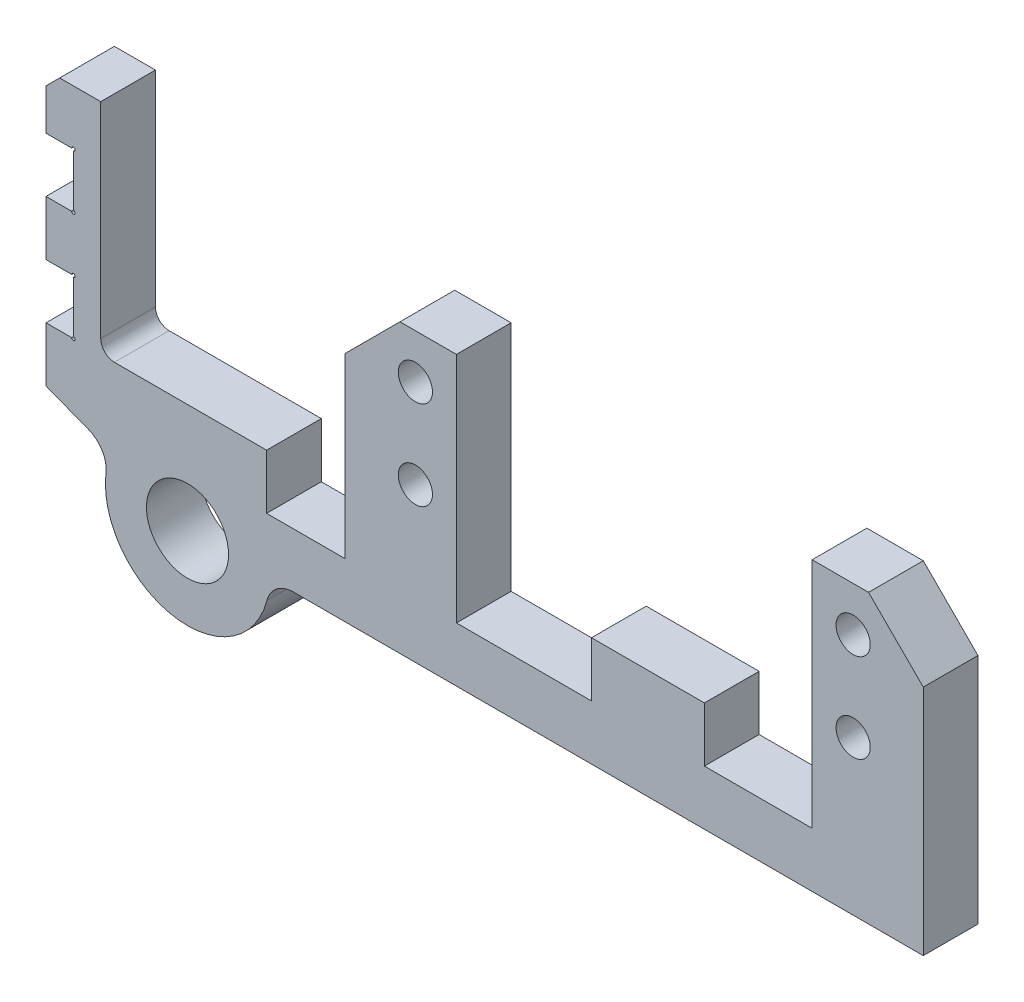
SolidWorks part; units mm, degrees
ref_plane "Front Plane" through (0, 0, 0) normal (0, 0, 1) x (1, 0, 0)
ref_plane "Top Plane" through (0, 0, 0) normal (0, 1, 0) x (1, 0, 0)
ref_plane "Right Plane" through (0, 0, 0) normal (1, 0, 0) x (0, 0, -1)
sketch "Sketch1" plane through (0, 136.6763, 0) normal (0, 1, 0) x (1, 0, 0)
  line L0 (-27.651, -32.4827) -> (-27.651, -60.4545) construction
  line L1 (-103.851, -54.1033) -> (-90.951, -54.1033)
  line L2 (-103.851, -54.1033) -> (-103.851, -60.4533)
  line L3 (-103.851, -60.4533) -> (-90.951, -60.4533)
  line L4 (-90.951, -54.1033) -> (-90.951, -60.4533)
  line L5 (-68.926, -54.1033) -> (-81.826, -54.1033)
  line L6 (-68.926, -54.1033) -> (-68.926, -60.4533)
  line L7 (-68.926, -60.4533) -> (-81.826, -60.4533)
  line L8 (-81.826, -54.1033) -> (-81.826, -60.4533)
  line L9 (-53.251, -54.1033) -> (-40.151, -54.1033)
  line L10 (-53.251, -54.1033) -> (-53.251, -60.4533)
  line L11 (-53.251, -60.4533) -> (-40.151, -60.4533)
  line L12 (-40.151, -54.1033) -> (-40.151, -60.4533)
  line L13 (-27.651, -54.1033) -> (-14.751, -54.1033)
  line L14 (-27.651, -54.1033) -> (-27.651, -60.4533)
  line L15 (-27.651, -60.4533) -> (-14.751, -60.4533)
  line L16 (-14.751, -54.1033) -> (-14.751, -60.4533)
  dimension "D1" = 12.9
  dimension "D2" = 13.1
  dimension "D3" = 12.9
  dimension "D4" = 12.9
  dimension "D5" = 50.6
extrude "Boss-Extrude1" add sketch "Sketch1" against normal blind 6.35
sketch "Sketch2" plane through (0, 130.3263, 0) normal (0, -1, 0) x (-1, 0, 0)
  line L1 (103.851, -60.4533) -> (14.951, -60.4533)
  line L2 (103.851, -60.4533) -> (103.851, -54.1033)
  line L3 (103.851, -54.1033) -> (14.951, -54.1033)
  line L4 (14.951, -60.4533) -> (14.951, -54.1033)
  dimension "D1" = 6.35
  dimension "D2" = 88.9
extrude "Boss-Extrude2" add sketch "Sketch2" along normal blind 12.7
sketch "Sketch3" plane through (0, 136.6763, 0) normal (0, 1, 0) x (1, 0, 0)
  line L1 (-68.926, -54.1033) -> (-81.826, -54.1033)
  line L2 (-68.926, -54.1033) -> (-68.926, -60.4533)
  line L3 (-68.926, -60.4533) -> (-81.826, -60.4533)
  line L4 (-81.826, -54.1033) -> (-81.826, -60.4533)
  line L5 (-14.751, -54.1033) -> (-27.651, -54.1033)
  line L6 (-14.751, -54.1033) -> (-14.751, -60.4533)
  line L7 (-14.751, -60.4533) -> (-27.651, -60.4533)
  line L8 (-27.651, -54.1033) -> (-27.651, -60.4533)
extrude "Boss-Extrude3" add sketch "Sketch3" along normal up to surface (20.6375 mm away)
chamfer "Chamfer1" distance 6.35 angle 45 2 edges at (-14.751, 157.3138, 57.2783) (-81.826, 157.3138, 57.2783)
sketch "Sketch4" plane through (0, 0, 60.4533) normal (0, 0, 1) x (1, 0, 0)
  circle A0 centre (-73.6885, 152.1544) radius 1.9844
  circle A1 centre (-73.6885, 141.8357) radius 1.9844
  circle A2 centre (-22.8885, 141.8357) radius 1.9844
  circle A3 centre (-22.8885, 152.1544) radius 1.9844
extrude "Cut-Extrude1" cut sketch "Sketch4" against normal through all
sketch "Sketch12" plane through (-14.951, 0, 0) normal (1, 0, 0) x (0, 0, -1)
  line L1 (-60.4533, 117.6263) -> (-54.1033, 117.6263)
  line L2 (-60.4533, 117.6263) -> (-60.4533, 130.3263)
  line L3 (-60.4533, 130.3263) -> (-54.1033, 130.3263)
  line L4 (-54.1033, 117.6263) -> (-54.1033, 130.3263)
extrude "Boss-Extrude6" add sketch "Sketch12" along normal up to surface (0.2 mm away) up to face at (-14.751, 140.645, 57.2783)
sketch "Sketch13" plane through (0, 0, 60.4533) normal (0, 0, 1) x (1, 0, 0)
  line L0 (-14.751, 117.6263) -> (-14.751, 150.9638) construction
  line L1 (-103.851, 117.6263) -> (-14.751, 117.6263)
  line L2 (-103.851, 117.6263) -> (-103.851, 123.9763)
  line L3 (-103.851, 123.9763) -> (-14.751, 123.9763)
  line L4 (-14.751, 117.6263) -> (-14.751, 123.9763)
  dimension "D1" = 6.35
extrude "Cut-Extrude2" cut sketch "Sketch13" against normal through all
sketch "Sketch14" plane through (0, 0, 60.4533) normal (0, 0, 1) x (1, 0, 0)
  line L0 (-14.751, 123.9763) -> (-103.851, 123.9763) construction
  line L1 (-110.201, 162.0763) -> (-116.551, 162.0763)
  line L2 (-110.201, 162.0763) -> (-110.201, 136.6763)
  line L3 (-113.2709, 123.9763) -> (-116.551, 123.9763)
  line L4 (-116.551, 162.0763) -> (-116.551, 123.9763)
  line L6 (-103.851, 136.6763) -> (-110.201, 136.6763)
  line L7 (-103.851, 136.6763) -> (-103.851, 123.9763)
  line L8 (-103.851, 123.9763) -> (-113.2709, 123.9763)
  dimension "D1" = 38.1
  dimension "D2" = 6.35
  dimension "D3" = 6.35
extrude "Boss-Extrude7" add sketch "Sketch14" against normal blind 6.35
fillet "Fillet1" radius 1.5875 1 edges at (-110.201, 136.6763, 57.2783)
chamfer "Chamfer2" distance 1.5875 angle 45 1 edges at (-116.551, 162.0763, 57.2783)
sketch "Sketch16" plane through (0, 0, 60.4533) normal (0, 0, 1) x (1, 0, 0)
  line L0 (-116.551, 160.4888) -> (-116.551, 123.9763) construction
  line L1 (-116.551, 155.7263) -> (-113.376, 155.7263)
  line L2 (-116.551, 155.7263) -> (-116.551, 149.3763)
  line L3 (-116.551, 149.3763) -> (-113.376, 149.3763)
  line L4 (-113.376, 155.7263) -> (-113.376, 149.3763)
  line L5 (-110.201, 162.0763) -> (-114.9635, 162.0763) construction
  line L6 (-116.551, 143.0263) -> (-113.376, 143.0263)
  line L7 (-116.551, 143.0263) -> (-116.551, 136.6763)
  line L8 (-116.551, 136.6763) -> (-113.376, 136.6763)
  line L9 (-113.376, 143.0263) -> (-113.376, 136.6763)
  point P10 (-112.5822, 162.0763)
  dimension "D1" = 3.175
  dimension "D2" = 6.35
  dimension "D3" = 3.175
  dimension "D4" = 6.35
  dimension "D5" = 6.35
  dimension "D6" = 6.35
extrude "Cut-Extrude4" cut sketch "Sketch16" against normal blind 6.35
sketch "Sketch17" plane through (0, 0, 60.4533) normal (0, 0, 1) x (1, 0, 0)
  circle A0 centre (-113.376, 155.7263) radius 0.1984
  circle A1 centre (-113.376, 149.3763) radius 0.1984
  circle A2 centre (-113.376, 143.0263) radius 0.1984
  circle A3 centre (-113.376, 136.6763) radius 0.1984
  dimension "D1" = 0.3969
  dimension "D2" = 0.3969
  dimension "D3" = 0.3969
  dimension "D4" = 0.3969
extrude "Cut-Extrude5" cut sketch "Sketch17" against normal blind 6.35
sketch "Sketch18" plane through (0, 0, 60.4533) normal (0, 0, 1) x (1, 0, 0)
  line L0 (-116.551, 123.9763) -> (-116.551, 130.3263)
  line L1 (-116.551, 136.6763) -> (-116.551, 123.9763) construction
  line L2 (-116.551, 130.3263) -> (-100.1326, 123.9763)
  line L3 (-14.751, 123.9763) -> (-116.551, 123.9763) construction
  line L4 (-100.1326, 123.9763) -> (-116.551, 123.9763)
extrude "Cut-Extrude6" cut sketch "Sketch18" against normal blind 6.35
sketch "Sketch19" plane through (0, 0, 60.4533) normal (0, 0, 1) x (1, 0, 0)
  line L0 (-14.751, 123.9763) -> (-100.1326, 123.9763) construction
  circle A0 centre (-100.1326, 123.9763) radius 9.525
  dimension "D1" = 19.05
extrude "Boss-Extrude8" add sketch "Sketch19" against normal blind 6.35
fillet "Fillet2" radius 3.175 2 edges at (-90.6076, 123.9763, 57.2783) (-109.0163, 127.4122, 57.2783)
sketch "Sketch20" plane through (0, 0, 60.4533) normal (0, 0, 1) x (1, 0, 0)
  circle A0 centre (-100.1326, 123.9763) radius 4.7625
extrude "Cut-Extrude7" cut sketch "Sketch20" against normal blind 6.35
